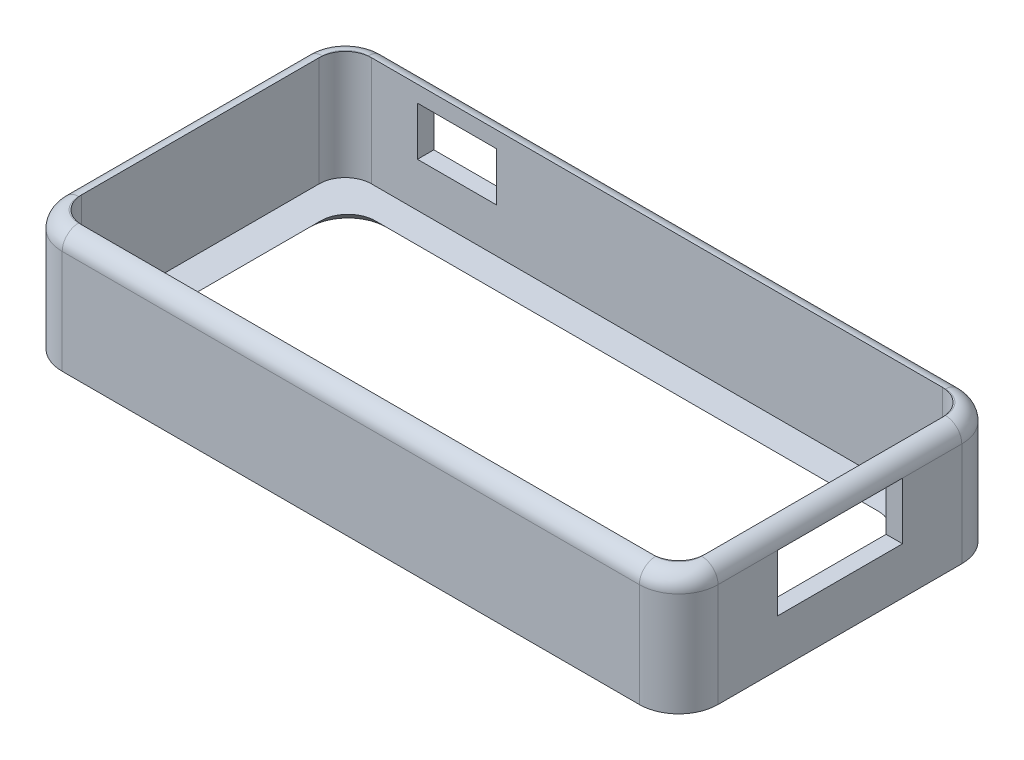
SolidWorks part; units mm, degrees
ref_plane "Alzado" through (0, 0, 0) normal (0, 0, 1) x (1, 0, 0)
ref_plane "Planta" through (0, 0, 0) normal (0, 1, 0) x (1, 0, 0)
ref_plane "Vista lateral" through (0, 0, 0) normal (1, 0, 0) x (0, 0, -1)
sketch "Croquis1" plane through (0, 0, 0) normal (0, 1, 0) x (1, 0, 0)
  line L1 (-52.8, 29.5) -> (52.8, 29.5)
  line L2 (-60, 22.3) -> (-60, -22.3)
  line L3 (-52.8, -29.5) -> (52.8, -29.5)
  line L4 (60, 22.3) -> (60, -22.3)
  line L5 (-52.2254, 26.5) -> (52.2254, 26.5)
  line L6 (-57, 21.7254) -> (-57, -21.7254)
  line L7 (-52.2254, -26.5) -> (52.2254, -26.5)
  line L8 (57, 21.7254) -> (57, -21.7254)
  arc A0 (57, 21.7254) -> (52.2254, 26.5) centre (52.2254, 21.7254) ccw
  arc A1 (52.2254, -26.5) -> (57, -21.7254) centre (52.2254, -21.7254) ccw
  arc A2 (-52.2254, -26.5) -> (-57, -21.7254) centre (-52.2254, -21.7254) cw
  arc A3 (-57, 21.7254) -> (-52.2254, 26.5) centre (-52.2254, 21.7254) cw
  arc A4 (-52.8, -29.5) -> (-60, -22.3) centre (-52.8, -22.3) cw
  arc A5 (52.8, -29.5) -> (60, -22.3) centre (52.8, -22.3) ccw
  arc A6 (60, 22.3) -> (52.8, 29.5) centre (52.8, 22.3) ccw
  arc A7 (-52.8, 29.5) -> (-60, 22.3) centre (-52.8, 22.3) ccw
  point P4 (0, 29.5)
  point P6 (60, 0)
  point P11 (0, 26.5)
  point P12 (57, 0)
  point P15 (57, 26.5)
  point P20 (-57, -26.5)
  point P23 (-57, 26.5)
  point P26 (-60, -29.5)
  point P31 (60, 29.5)
  point P34 (-60, 29.5)
  dimension "D5" = 4.7746
  dimension "D6" = 7.2
  dimension "D1" = 120
  dimension "D2" = 59
  dimension "D3" = 114
  dimension "D4" = 53
extrude "Saliente-Extruir2" add sketch "Croquis1" along normal blind 22
sketch "Croquis2" plane through (0, 0, 0) normal (0, -1, 0) x (1, 0, 0)
  line L4 (-60, 22.3) -> (-60, -22.3)
  line L5 (-52.8, -29.5) -> (52.8, -29.5)
  line L6 (60, -22.3) -> (60, 22.3)
  line L7 (52.8, 29.5) -> (-52.8, 29.5)
  line L8 (-60, 22.3) -> (-60, -22.3)
  line L9 (-52.8, -29.5) -> (52.8, -29.5)
  line L10 (60, -22.3) -> (60, 22.3)
  line L11 (52.8, 29.5) -> (-52.8, 29.5)
  arc A4 (-52.8, 29.5) -> (-60, 22.3) centre (-52.8, 22.3) ccw
  arc A5 (-60, -22.3) -> (-52.8, -29.5) centre (-52.8, -22.3) ccw
  arc A6 (52.8, -29.5) -> (60, -22.3) centre (52.8, -22.3) ccw
  arc A7 (60, 22.3) -> (52.8, 29.5) centre (52.8, 22.3) ccw
  arc A8 (-52.8, 29.5) -> (-60, 22.3) centre (-52.8, 22.3) ccw
  arc A9 (-60, -22.3) -> (-52.8, -29.5) centre (-52.8, -22.3) ccw
  arc A10 (52.8, -29.5) -> (60, -22.3) centre (52.8, -22.3) ccw
  arc A11 (60, 22.3) -> (52.8, 29.5) centre (52.8, 22.3) ccw
  dimension "D1" = 0
extrude "Saliente-Extruir3" add sketch "Croquis2" against normal blind 2
sketch "Croquis3" plane through (0, 2, 0) normal (0, 1, 0) x (1, 0, 0)
  line L1 (-46, 20) -> (46, 20)
  line L2 (-50, 16) -> (-50, -16)
  line L3 (-46, -20) -> (46, -20)
  line L4 (50, 16) -> (50, -16)
  arc A0 (-46, 20) -> (-50, 16) centre (-46, 16) ccw
  arc A1 (-46, -20) -> (-50, -16) centre (-46, -16) cw
  arc A2 (46, -20) -> (50, -16) centre (46, -16) ccw
  arc A3 (50, 16) -> (46, 20) centre (46, 16) ccw
  point P4 (0, 20)
  point P6 (50, 0)
  point P10 (-50, 20)
  point P13 (-50, -20)
  point P18 (50, 20)
  dimension "D3" = 4
  dimension "D4" = 4
  dimension "D1" = 100
  dimension "D2" = 40
extrude "Cortar-Extruir1" cut sketch "Croquis3" against normal blind 2
chamfer "Chaflán1" distance 3 angle 45 8 edges at (-50, 0, 0) (-48.8284, 0, 18.8284) (-48.8284, 0, -18.8284) (0, 0, 20) (0, 0, -20) (48.8284, 0, 18.8284) (48.8284, 0, -18.8284) (50, 0, 0)
fillet "Redondeo2" radius 3 8 edges at (57.8912, 22, -27.3912) (60, 22, 0) (57.8912, 22, 27.3912) (0, 22, 29.5) (-57.8912, 22, 27.3912) (-60, 22, 0) (-57.8912, 22, -27.3912) (0, 22, -29.5)
sketch "Croquis4" plane through (60, 0, 0) normal (1, 0, 0) x (0, 0, -1)
  line L1 (-11.45, 19) -> (11.45, 19)
  line L2 (-11.45, 19) -> (-11.45, 8.6)
  line L3 (-11.45, 8.6) -> (11.45, 8.6)
  line L4 (11.45, 19) -> (11.45, 8.6)
  line L5 (22.3, 19) -> (-22.3, 19) construction
  point P4 (0, 8.6)
  dimension "D1" = 22.9
  dimension "D2" = 10.4
extrude "Cortar-Extruir2" cut sketch "Croquis4" against normal blind 10
sketch "Croquis5" plane through (0, 0, -29.5) normal (0, 0, -1) x (-1, 0, 0)
  line L0 (52.8, 19) -> (52.8, 0) construction
  line L1 (29.3, 19) -> (43.8, 19)
  line L2 (29.3, 19) -> (29.3, 10.1)
  line L3 (29.3, 10.1) -> (43.8, 10.1)
  line L4 (43.8, 19) -> (43.8, 10.1)
  line L5 (52.8, 19) -> (-52.8, 19) construction
  dimension "D1" = 14.5
  dimension "D2" = 8.9
  dimension "D3" = 9
extrude "Cortar-Extruir3" cut sketch "Croquis5" against normal blind 10
